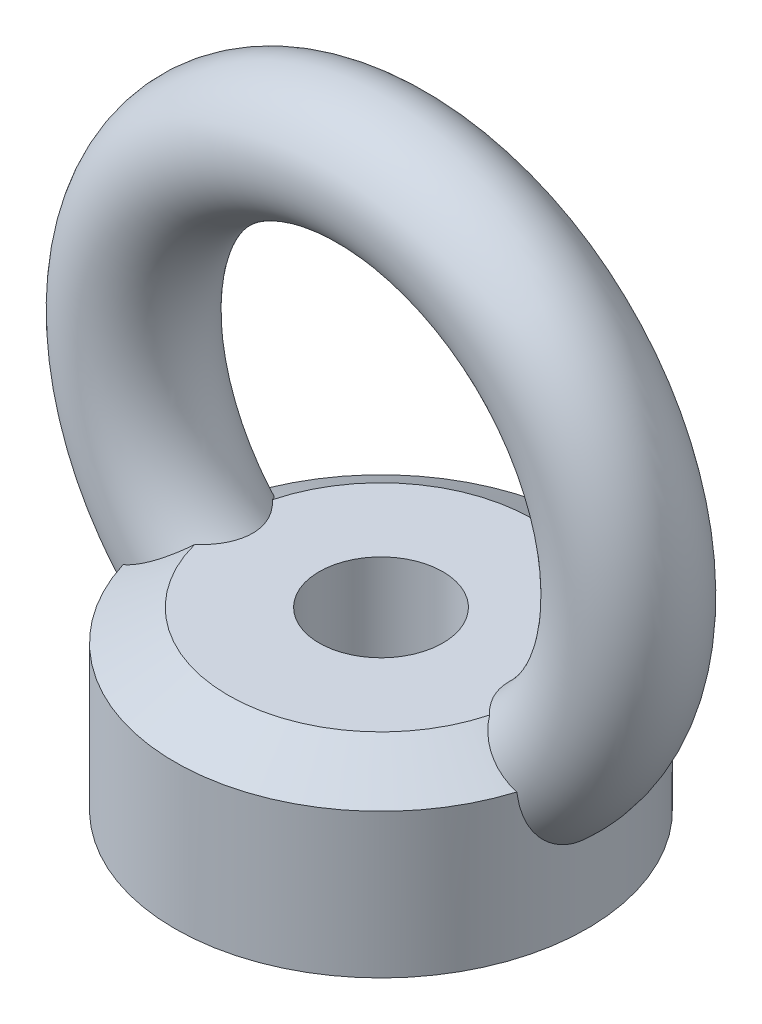
SolidWorks part; units mm, degrees
material "AISI 1020"
ref_plane "Front Plane" through (0, 0, 0) normal (0, 0, 1) x (1, 0, 0)
ref_plane "Top Plane" through (0, 0, 0) normal (0, 1, 0) x (1, 0, 0)
ref_plane "Right Plane" through (0, 0, 0) normal (1, 0, 0) x (0, 0, -1)
sketch "Sketch4" plane through (0, 0, 0) normal (0, 1, 0) x (1, 0, 0)
  line L0 (0, 0) -> (16.2266, 0) construction
  line L1 (0, -4.7219) -> (0, 12.5068) construction
  circle A0 centre (12, 0) radius 3
  point P5 (9, 0)
  point P6 (15, 0)
  dimension "D1" = 6
  dimension "D2" = 15
revolve "Revolve2" add sketch "Sketch4" angle 360 about L1
ref_plane "Plane2" through (0, -15, 0) normal (0, 1, 0) x (1, 0, 0)
sketch "Sketch5" plane through (0, -15, 0) normal (0, 1, 0) x (1, 0, 0)
  circle A0 centre (0, 0) radius 10
  dimension "D1" = 20
extrude "Boss-Extrude2" add sketch "Sketch5" along normal blind 8.5
chamfer "Chamfer1" distance 1.5 angle 60 2 edges at (0, -6.5, -10) (0, -6.5, 10) first distance on face at (0, -8.8392, 0)
sketch "Sketch6" plane through (0, -15, 0) normal (0, -1, 0) x (1, 0, 0)
  circle A0 centre (0, 0) radius 3
  dimension "D1" = 6
extrude "Cut-Extrude1" cut sketch "Sketch6" against normal blind 8.5
